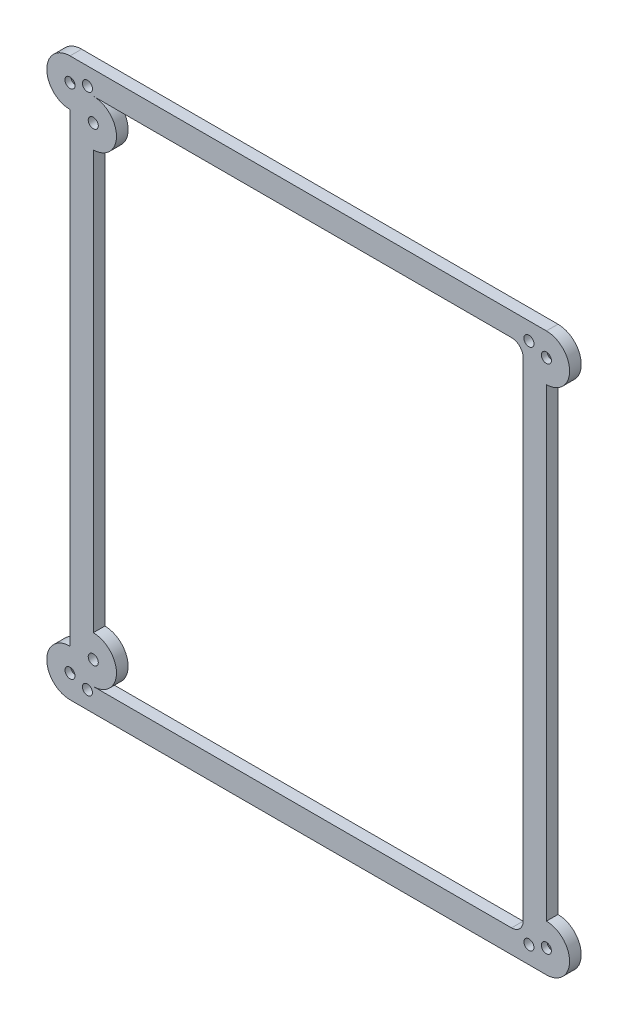
SolidWorks part; units mm, degrees
ref_plane "Front Plane" through (0, 0, 0) normal (0, 0, 1) x (1, 0, 0)
ref_plane "Top Plane" through (0, 0, 0) normal (0, 1, 0) x (1, 0, 0)
ref_plane "Right Plane" through (0, 0, 0) normal (1, 0, 0) x (0, 0, -1)
sketch "Sketch1" plane through (0, 0, 0) normal (0, 0, 1) x (1, 0, 0)
  line L0 (254, 6.35) -> (254, -273.05) construction
  line L1 (-19.05, -285.75) -> (241.3, -285.75)
  line L2 (-19.05, -285.75) -> (-19.05, 19.05)
  line L3 (-19.05, 19.05) -> (241.3, 19.05)
  line L4 (241.3, -285.75) -> (241.3, 19.05)
  line L5 (-19.05, -285.75) -> (241.3, 19.05) construction
  line L6 (-19.05, 19.05) -> (241.3, -285.75) construction
  line L7 (-6.35, 6.35) -> (228.6, 6.35)
  line L8 (-6.35, 6.35) -> (-6.35, -273.05)
  line L9 (-6.35, -273.05) -> (228.6, -273.05)
  line L10 (228.6, 6.35) -> (228.6, -273.05)
  line L11 (-6.35, 6.35) -> (228.6, -273.05) construction
  line L12 (-6.35, -273.05) -> (228.6, 6.35) construction
  circle A0 centre (-9.525, -276.225) radius 2.75
  circle A1 centre (231.775, -276.225) radius 2.75
  circle A2 centre (231.775, 9.525) radius 2.75
  circle A3 centre (-9.525, 9.525) radius 2.75
  circle A4 centre (231.775, 9.525) radius 2.75 construction
  arc A5 (241.3, 19.05) -> (241.3, -6.35) centre (241.3, 6.35) cw
  arc A6 (241.3, -260.35) -> (241.3, -285.75) centre (241.3, -273.05) cw
  arc A7 (-19.05, 19.05) -> (-19.05, -6.35) centre (-19.05, 6.35) ccw
  arc A8 (-19.05, -285.75) -> (-19.05, -260.35) centre (-19.05, -273.05) cw
  circle A9 centre (-19.05, -273.05) radius 2.75
  circle A10 centre (241.3, -273.05) radius 2.75
  circle A11 centre (241.3, 6.35) radius 2.75
  circle A12 centre (-19.05, 6.35) radius 2.75
  circle A13 centre (-6.35, -260.35) radius 2.75
  circle A14 centre (-6.35, -260.35) radius 12.7
  circle A15 centre (-6.35, -6.35) radius 12.7
  circle A16 centre (-6.35, -6.35) radius 2.75
  point P4 (111.125, -133.35)
  point P24 (111.125, -133.35)
  dimension "D1" = 12.7
  dimension "D2" = 12.7
  dimension "D3" = 12.7
extrude "Boss-Extrude1" add sketch "Sketch1" along normal blind 6.35 contours L1 L4 L3 L2 A3 A2 A1 A0 L7 L10 L9 L8 | A6 L4 | A5 L4 | A9 L2 A8 | A12 L2 A7 | A15 L2 A14 L8 | A16 L8 A15 | A16 L8 A15 | L8 A14 A13 | L8 A14 A13 region at (-15.0414, -280.775, 0) region at (-24.6478, -273.05, 0) region at (246.8978, -273.05, 0) region at (-11.9478, -260.35, 0) region at (-12.7818, -133.35, 0) region at (-24.6478, 6.35, 0) region at (-11.9478, -6.35, 0) region at (-0.7522, -260.35, 0) region at (246.8978, 6.35, 0) region at (-0.7522, -6.35, 0)
fillet "Fillet1" radius 6.35 2 edges at (228.6, 6.35, 3.175) (228.6, -273.05, 3.175)
chamfer "Chamfer1" distance 3.175 angle 45 4 edges at (-16.3, 6.35, 0) (244.05, 6.35, 0) (244.05, -273.05, 0) (-16.3, -273.05, 0)
